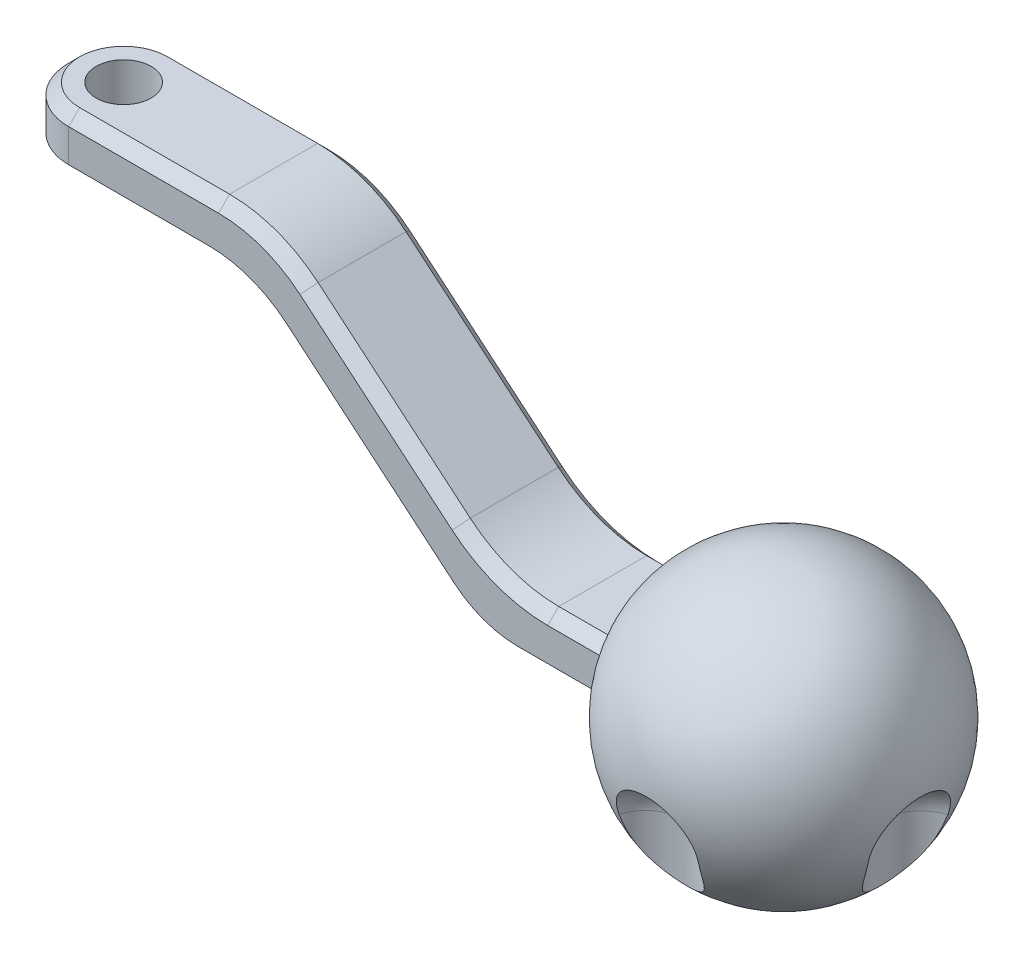
SolidWorks part; units mm, degrees
ref_plane "Front Plane" through (0, 0, 0) normal (0, 0, 1) x (1, 0, 0)
ref_plane "Top Plane" through (0, 0, 0) normal (0, 1, 0) x (1, 0, 0)
ref_plane "Right Plane" through (0, 0, 0) normal (1, 0, 0) x (0, 0, -1)
sketch "Sketch2" plane through (0, 0, 0) normal (0, 0, 1) x (1, 0, 0)
  line L0 (0, 31.75) -> (0, 0)
  line L1 (0, 0) -> (0, -31.75)
  arc A0 (0, -31.75) -> (0, 31.75) centre (0, 0) ccw
  dimension "D1" = 63.5
revolve "Revolve1" add sketch "Sketch2" angle 360 about L0
sketch "Sketch7" plane through (0, 0, 0) normal (0, 1, 0) x (1, 0, 0)
  line L0 (31.7498, -0.0977) -> (-0.0279, -0.0977) construction
  line L1 (-0.0279, 31.75) -> (-0.0279, -0.0977) construction
  line L2 (-0.0279, -0.0977) -> (-0.0279, -31.75) construction
  circle A0 centre (31.7498, -0.0977) radius 9.525
  circle A1 centre (-0.0279, 31.75) radius 9.525
  circle A2 centre (-0.0279, -31.75) radius 9.525
  circle A3 centre (0, 0) radius 31.75 construction
  circle A4 centre (0, 0) radius 31.75 construction
  dimension "D1" = 19.05
  dimension "D2" = 19.05
  dimension "D3" = 19.05
extrude "Cut-Extrude1" cut sketch "Sketch7" against normal blind 40.64
sketch "Sketch10" plane through (0, 0, 0) normal (1, 0, 0) x (0, 0, -1)
  line L1 (-12.7, 6.35) -> (12.7, 6.35)
  line L2 (-12.7, 6.35) -> (-12.7, -6.35)
  line L3 (-12.7, -6.35) -> (12.7, -6.35)
  line L4 (12.7, 6.35) -> (12.7, -6.35)
  line L5 (-12.7, 6.35) -> (12.7, -6.35) construction
  line L6 (-12.7, -6.35) -> (12.7, 6.35) construction
  point P0 (0, 0)
  dimension "D1" = 12.7
  dimension "D2" = 25.4
fillet "Fillet4" radius 9.525 3 edges at (-0.0195, 0, -22.225) (22.2249, 0, 0.0684) (-0.0195, 0, 22.225)
sketch "Sketch15" plane through (0, 0, 0) normal (0, 0, 1) x (1, 0, 0)
  line L0 (0, 0) -> (0, 6.35)
  line L1 (0, 6.35) -> (-53.34, 6.35)
  line L2 (-53.34, 6.35) -> (-106.1974, 50.8)
  line L3 (-106.1974, 50.8) -> (-165.1, 50.8)
  line L4 (-10.9985, -6.35) -> (-10.9985, -6.35)
  line L5 (-10.9985, -6.35) -> (-57.9702, -6.35)
  line L6 (-57.9702, -6.35) -> (-110.8276, 38.1)
  line L7 (-110.8276, 38.1) -> (-165.1, 38.1)
  line L8 (-10.9985, -6.35) -> (0, -6.35)
  line L9 (0, 6.35) -> (0, -6.35) construction
  line L10 (0, -6.35) -> (0, 6.35) construction
  line L11 (0, -6.35) -> (0, 0)
  line L12 (-165.1, 50.8) -> (-165.1, 38.1)
  dimension "D1" = 6.35
  dimension "D2" = 53.34
  dimension "D3" = 106.1974
  dimension "D4" = 165.1
  dimension "D5" = 50.8
  dimension "D6" = 12.7
extrude "Boss-Extrude4" add sketch "Sketch15" along normal mid plane 25.4
fillet "Fillet5" radius 31.75 2 edges at (-106.1974, 50.8, 0) (-53.34, 6.35, 0)
fillet "Fillet6" radius 25.4 2 edges at (-110.8276, 38.1, 0) (-57.9702, -6.35, 0)
sketch "Sketch16" plane through (0, 0, 0) normal (0, 1, 0) x (1, 0, 0)
  line L3 (-152.4, 12.7) -> (-183.5156, 12.7)
  line L4 (-183.5156, 12.7) -> (-183.5156, -12.7)
  line L5 (-183.5156, -12.7) -> (-152.4, -12.7)
  arc A0 (-152.4, 12.7) -> (-152.4, -12.7) centre (-152.4, 0) ccw
  dimension "D1" = 12.7
  dimension "D2" = 152.4
extrude "Cut-Extrude4" cut sketch "Sketch16" along normal blind 78.74
sketch "Sketch17" plane through (0, 0, 0) normal (0, 1, 0) x (1, 0, 0)
  line L0 (0, 0) -> (-165.1, 0) construction
  arc A0 (-152.4, 12.7) -> (-152.4, -12.7) centre (-152.4, 0) ccw construction
  circle A1 centre (-152.4, 0) radius 6.35
  point P8 (0, 0)
  dimension "D1" = 12.7
  dimension "D2" = 152.4
extrude "Cut-Extrude5" cut sketch "Sketch17" along normal blind 78.74
chamfer "Chamfer1" distance 2.54 angle 45 22 edges at (-38.5539, -6.35, 12.7) (-57.41, -4.8135, 12.7) (-84.3989, 15.875, 12.7) (-111.3878, 36.5635, 12.7) (-136.244, 38.1, 12.7) (-165.1, 38.1, 0) (-136.244, 38.1, -12.7) (-111.3878, 36.5635, -12.7) (-84.3989, 15.875, -12.7) (-57.41, -4.8135, -12.7) (-38.5539, -6.35, -12.7) (-35.0813, 6.35, -12.7) (-52.6398, 8.2706, -12.7) (-79.7687, 28.575, -12.7) (-106.8976, 48.8794, -12.7) (-135.0864, 50.8, -12.7) (-165.1, 50.8, 0) (-135.0864, 50.8, 12.7) (-106.8976, 48.8794, 12.7) (-79.7687, 28.575, 12.7) (-52.6398, 8.2706, 12.7) (-35.0813, 6.35, 12.7)
